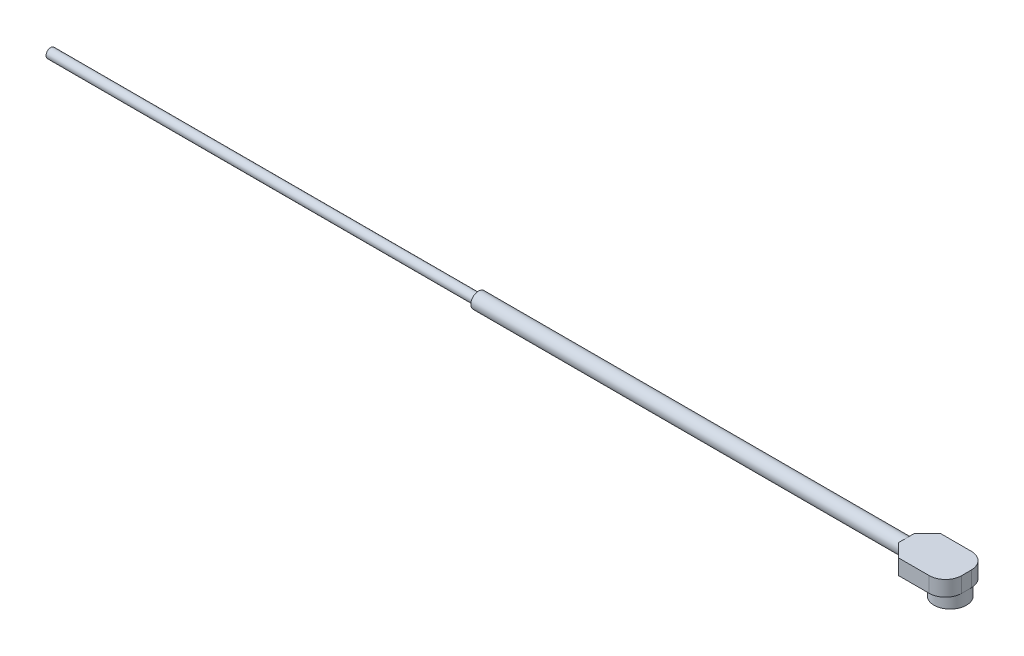
SolidWorks part; units mm, degrees
ref_plane "Front Plane" through (0, 0, 0) normal (0, 0, 1) x (1, 0, 0)
ref_plane "Top Plane" through (0, 0, 0) normal (0, 1, 0) x (1, 0, 0)
ref_plane "Right Plane" through (0, 0, 0) normal (1, 0, 0) x (0, 0, -1)
sketch "Sketch1" plane through (0, 0, 0) normal (0, 1, 0) x (1, 0, 0)
  line L1 (-2.25, -1.575) -> (2.25, -1.575)
  line L2 (-2.25, -1.575) -> (-2.25, 1.575)
  line L3 (-2.25, 1.575) -> (2.25, 1.575)
  line L4 (2.25, -1.575) -> (2.25, 1.575)
  line L5 (-2.25, -1.575) -> (2.25, 1.575) construction
  line L6 (-2.25, 1.575) -> (2.25, -1.575) construction
  point P0 (0, 0)
  dimension "D1" = 3.15
  dimension "D2" = 4.5
extrude "Boss-Extrude1" add sketch "Sketch1" along normal blind 1.15
sketch "Sketch2" plane through (0, 0, 0) normal (0, -1, 0) x (1, 0, 0)
  line L0 (2.25, 1.575) -> (2.25, -1.575) construction
  line L1 (1.035, 1.215) -> (1.035, 1.05) construction
  line L2 (1.035, 0.25) -> (1.035, 0.415) construction
  circle A0 centre (1.035, 0) radius 1.215
  circle A1 centre (1.035, 0) radius 1.05
  circle A2 centre (1.035, 0) radius 0.25
  circle A3 centre (1.035, 0) radius 0.415
  point P2 (1.035, 1.05)
  point P7 (1.035, 1.215)
  point P12 (1.035, 0.415)
  point P13 (1.035, 0.25)
  dimension "D1" = 2.43
  dimension "D2" = 2.1
  dimension "D3" = 0.5
extrude "Boss-Extrude2" add sketch "Sketch2" along normal blind 2.1 from surface contours A3 A2 | A0 A1 region at (-0.1456, 0, 0) region at (0.6317, 0, 0) starting at face at (0, 1.15, 0)
sketch "Sketch3" plane through (-2.25, 0, 0) normal (-1, 0, 0) x (0, 0, 1)
  line L0 (-1.575, 0) -> (1.575, 1.15) construction
  circle A0 centre (0, 0.575) radius 0.575
  point P6 (0, 0.575)
  dimension "D1" = 1.15
extrude "Boss-Extrude3" add sketch "Sketch3" along normal blind 32
sketch "Sketch4" plane through (-34.25, 0, 0) normal (-1, 0, 0) x (0, 0, 1)
  circle A0 centre (0, 0.575) radius 0.35
  circle A1 centre (0, 0.575) radius 0.575 construction
  dimension "D1" = 0.7
extrude "Boss-Extrude4" add sketch "Sketch4" along normal blind 32
fillet "Fillet1" radius 1.215 2 edges at (2.25, 0.575, -1.575) (2.25, 0.575, 1.575)
chamfer "Chamfer2" distance 1 angle 45 2 edges at (-2.25, 0.575, 1.575) (-2.25, 0.575, -1.575)
